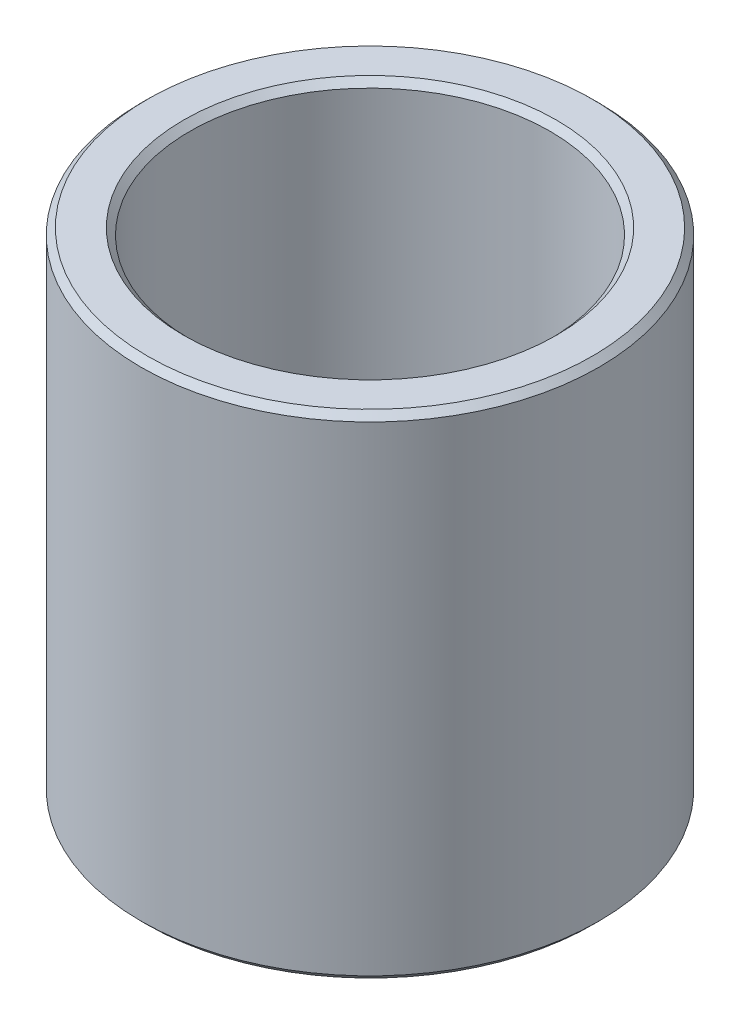
SolidWorks part; units mm, degrees
ref_plane "Front Plane" through (0, 0, 0) normal (0, 0, 1) x (1, 0, 0)
ref_plane "Top Plane" through (0, 0, 0) normal (0, 1, 0) x (1, 0, 0)
ref_plane "Right Plane" through (0, 0, 0) normal (1, 0, 0) x (0, 0, -1)
sketch "Sketch1" plane through (0, 0, 0) normal (0, 1, 0) x (1, 0, 0)
  circle A0 centre (0, 0) radius 42.5
  dimension "SLEEVE_OD" = 85
extrude "Boss-Extrude1" add sketch "Sketch1" along normal blind 91.4364
sketch "Sketch2" plane through (0, 0, 0) normal (0, 1, 0) x (1, 0, 0)
  circle A0 centre (0, 0) radius 33.4186
  dimension "BORE_D" = 66.8373
extrude "Cut-Extrude1" cut sketch "Sketch2" along normal through all
chamfer "Chamfer1" distance 1.1945 angle 45 4 edges at (0, 91.4364, 33.4186) (0, 0, 33.4186) (0, 0, 42.5) (0, 91.4364, 42.5)
